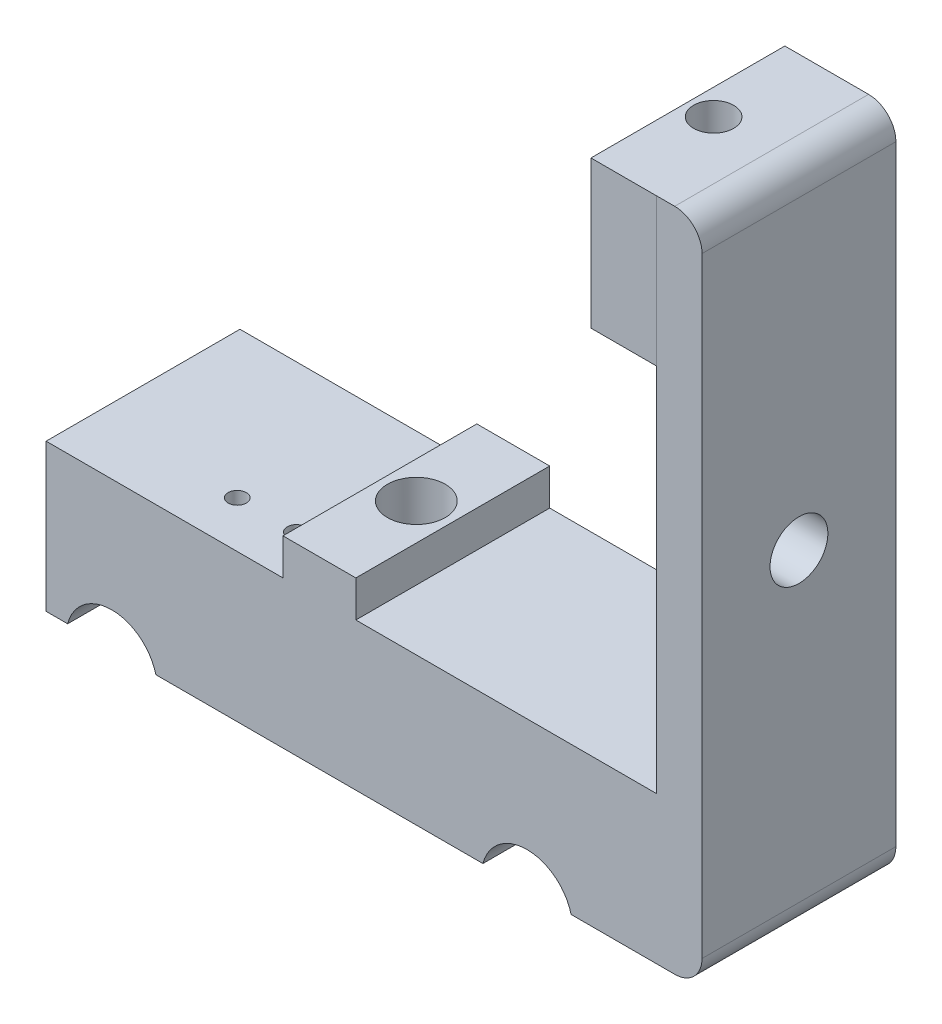
SolidWorks part; units mm, degrees
ref_plane "Front Plane" through (0, 0, 0) normal (0, 0, 1) x (1, 0, 0)
ref_plane "Top Plane" through (0, 0, 0) normal (0, 1, 0) x (1, 0, 0)
ref_plane "Right Plane" through (0, 0, 0) normal (1, 0, 0) x (0, 0, -1)
sketch "Sketch2" plane through (0, 0, 0) normal (0, 0, 1) x (1, 0, 0)
  line L0 (10.1, 0) -> (-10.1, 0)
  line L1 (-10.1, 0) -> (-10.1, 1.7099)
  line L2 (-10.1, 1.7099) -> (-6.2548, 7)
  line L3 (-6.2548, 7) -> (6.2548, 7)
  line L4 (0, 7) -> (0, 0)
  line L5 (0, 0) -> (0, 9.2516) construction
  line L6 (10.1, 1.7099) -> (6.2548, 7)
  line L7 (10.1, 0) -> (10.1, 1.7099)
  dimension "D1" = 20.2
  dimension "D2" = 7
extrude "Boss-Extrude1" add sketch "Sketch2" along normal blind 10.8 contours L4 L3 L2 L1 L0 | L0 L7 L6 L3 L4 region at (4.4168, 3.2082, 0) region at (-4.4168, 3.2082, 0)
sketch "Sketch4" plane through (0, 0, 0) normal (0, 0, 1) x (1, 0, 0)
  line L0 (-4, 0) -> (-4, -4.8)
  line L1 (10.1, 0) -> (-10.1, 0) construction
  line L2 (-4, -4.8) -> (-30, -4.8)
  line L3 (-30, -4.8) -> (-30, -29.8)
  line L4 (-30, -29.8) -> (30, -29.8)
  line L5 (0, 0) -> (0, -29.8) construction
  line L6 (0, -29.8) -> (0, 0)
  line L7 (4, 0) -> (-4, 0)
  line L8 (0, 0) -> (0, -30.5381) construction
  line L9 (30, -4.8) -> (30, -29.8)
  line L10 (4, -4.8) -> (30, -4.8)
  line L11 (4, 0) -> (4, -4.8)
  line L13 (-30, -20.98) -> (30, -20.98)
  line L14 (-30, -20.98) -> (-30, -23.48)
  line L15 (-30, -23.48) -> (30, -23.48)
  line L16 (30, -20.98) -> (30, -23.48)
  dimension "D1" = 4.8
  dimension "D2" = 4
  dimension "D3" = 25
  dimension "D4" = 60
  dimension "D6" = 8.82
extrude "Boss-Extrude2" add sketch "Sketch4" along normal mid plane 21.28 contours L6 L7 L0 L2 L3 L4 | L11 L7 L6 L4 L9 L10 region at (-14.5054, -12.4909, 0) region at (14.5054, -12.4909, 0)
sketch "Sketch5" plane through (0, 0, 0) normal (0, 0, 1) x (1, 0, 0)
  line L0 (-29.791, -22.2274) -> (26.9734, -22.2274) construction
  line L3 (0, -20.98) -> (0, 7) construction
  line L5 (-6.2548, 7) -> (6.2548, 7) construction
  line L20 (-30, -20.98) -> (30, -20.98) construction
  circle A0 centre (-22.791, -22.2274) radius 5
  circle A1 centre (22.791, -22.2274) radius 5
  dimension "D1" = 7
extrude "Cut-Extrude1" cut sketch "Sketch5" along normal through all both and the other way through all
fillet "Fillet1" radius 1 6 edges at (-10.1, 0, 5.4) (-10.1, 1.7099, 5.4) (-6.2548, 7, 5.4) (6.2548, 7, 5.4) (10.1, 0, 5.4) (10.1, 1.7099, 5.4)
sketch "Sketch6" plane through (30, 0, 0) normal (1, 0, 0) x (0, 0, -1)
  line L0 (-10.64, -20.98) -> (10.64, -20.98) construction
  line L1 (-10.64, -4.8) -> (10.64, -4.8)
  line L2 (-10.64, -4.8) -> (-10.64, -20.98)
  line L3 (-10.64, -20.98) -> (10.64, -20.98)
  line L4 (10.64, -4.8) -> (10.64, -20.98)
extrude "Boss-Extrude3" add sketch "Sketch6" along normal blind 12
sketch "Sketch7" plane through (0, -4.8, 0) normal (0, 1, 0) x (1, 0, 0)
  line L0 (4, -10.64) -> (42, -10.64) construction
  line L1 (42, 10.6413) -> (37, 10.6413)
  line L2 (42, 10.6413) -> (42, -10.64)
  line L3 (42, -10.64) -> (37, -10.64)
  line L4 (37, 10.6413) -> (37, -10.64)
  dimension "D1" = 5
extrude "Boss-Extrude4" add sketch "Sketch7" along normal blind 56.83
sketch "Sketch8" plane through (37, 0, 0) normal (-1, 0, 0) x (0, 0, 1)
  line L0 (-10.6413, 52.03) -> (-10.6413, -4.8) construction
  line L1 (10.643, 52.03) -> (-10.6413, 52.03)
  line L2 (10.643, 52.03) -> (10.643, 35.85)
  line L3 (10.643, 35.85) -> (-10.6413, 35.85)
  line L4 (-10.6413, 52.03) -> (-10.6413, 35.85)
  dimension "D1" = 16.18
extrude "Boss-Extrude5" add sketch "Sketch8" along normal blind 7.19
fillet "Fillet3" radius 3 2 edges at (42, 52.03, -0.0007) (42, -20.98, 0)
sketch "Sketch9" plane through (0, -20.98, 0) normal (0, -1, 0) x (1, 0, 0)
  line L0 (27.6329, 0) -> (27.6329, 10.8) construction
  line L2 (27.6329, 10.64) -> (39, 10.64) construction
  circle A0 centre (32.6329, 0) radius 2.2
  dimension "D1" = 5
  dimension "D2" = 10.64
extrude "Cut-Extrude2" cut sketch "Sketch9" against normal through all
sketch "Sketch10" plane through (0, -20.98, 0) normal (0, -1, 0) x (1, 0, 0)
  line L2 (-17.9491, 0) -> (-17.9491, 10.8) construction
  line L3 (-17.9491, 10.64) -> (17.9491, 10.64) construction
  circle A0 centre (0.0009, 0) radius 3.175
  dimension "D1" = 10.64
  dimension "D2" = 17.95
extrude "Cut-Extrude3" cut sketch "Sketch10" against normal through all
sketch "Sketch11" plane through (0, 0, 10.8) normal (0, 0, 1) x (1, 0, 0)
  line L0 (9.1, 0) -> (-9.1, 0) construction
  line L1 (-12.6098, 8.9215) -> (12.3675, 8.9215)
  line L2 (-12.6098, 8.9215) -> (-12.6098, -0.8)
  line L3 (-12.6098, -0.8) -> (12.3675, -0.8)
  line L4 (12.3675, 8.9215) -> (12.3675, -0.8)
  dimension "D1" = 0.8
extrude "Cut-Extrude4" cut sketch "Sketch11" against normal through all
sketch "Sketch12" plane through (0, -20.98, 0) normal (0, -1, 0) x (1, 0, 0)
  arc A0 (-8.6262, 5.538) -> (-6.6262, 5.538) centre (-7.6262, 5.538) ccw construction
  arc A1 (-6.6262, 5.538) -> (-8.6262, 5.538) centre (-7.6262, 5.538) ccw construction
  arc A2 (-15.1262, 5.538) -> (-13.1262, 5.538) centre (-14.1262, 5.538) ccw construction
  arc A3 (-13.1262, 5.538) -> (-15.1262, 5.538) centre (-14.1262, 5.538) ccw construction
  arc A4 (-8.6262, 5.538) -> (-6.6262, 5.538) centre (-7.6262, 5.538) ccw
  arc A5 (-6.6262, 5.538) -> (-8.6262, 5.538) centre (-7.6262, 5.538) ccw
  arc A6 (-15.1262, 5.538) -> (-13.1262, 5.538) centre (-14.1262, 5.538) ccw
  arc A7 (-13.1262, 5.538) -> (-15.1262, 5.538) centre (-14.1262, 5.538) ccw
extrude "Cut-Extrude5" cut sketch "Sketch12" against normal up to next
sketch "Sketch13" plane through (42, 0, 0) normal (1, 0, 0) x (0, 0, -1)
  line L0 (10.6413, 49.03) -> (-10.64, 49.03) construction
  circle A0 centre (0, 15.525) radius 3.175
  dimension "D1" = 33.505
extrude "Cut-Extrude6" cut sketch "Sketch13" against normal through all
